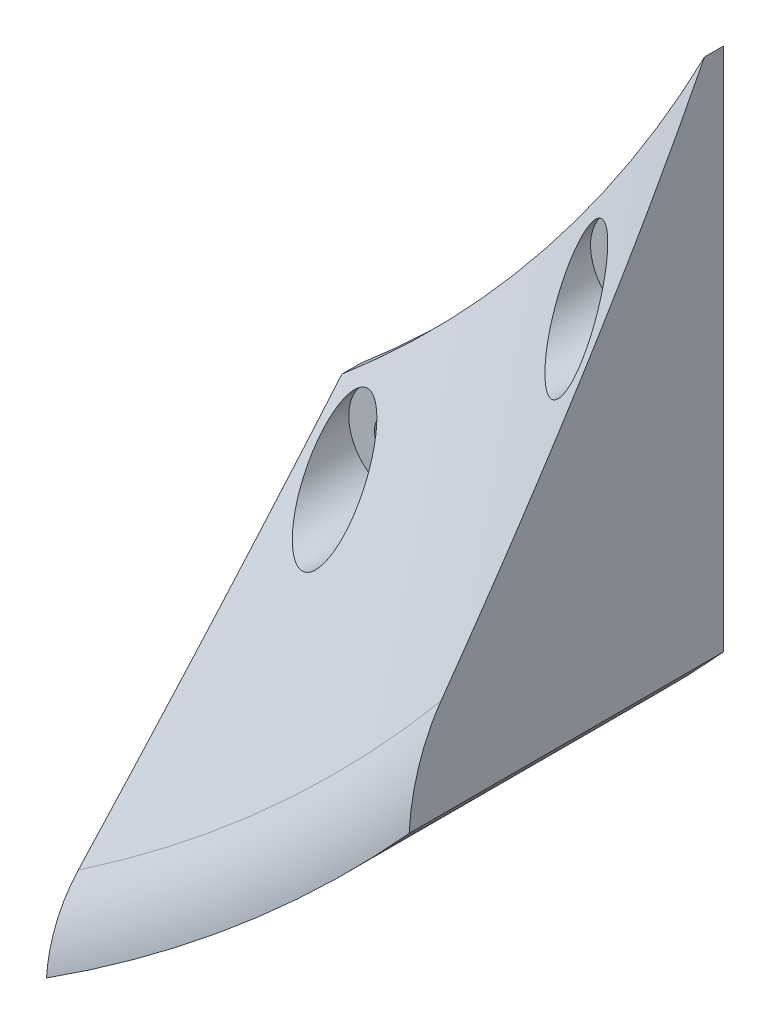
SolidWorks part; units mm, degrees
material "6061 Alloy"
ref_plane "Front Plane" through (0, 0, 0) normal (0, 0, 1) x (1, 0, 0)
ref_plane "Top Plane" through (0, 0, 0) normal (0, 1, 0) x (1, 0, 0)
ref_plane "Right Plane" through (0, 0, 0) normal (1, 0, 0) x (0, 0, -1)
sketch "Sketch1" plane through (0, 0, 0) normal (0, 0, 1) x (1, 0, 0)
  line L1 (-140.9655, 145.0225) -> (-102.8655, 145.0225)
  line L2 (-140.9655, 145.0225) -> (-140.9655, -145.0225)
  line L3 (-140.9655, -145.0225) -> (-102.8655, -145.0225)
  line L4 (-102.8655, 145.0225) -> (-102.8655, -145.0225)
  line L5 (-140.9655, 145.0225) -> (-102.8655, -145.0225) construction
  line L6 (-140.9655, -145.0225) -> (-102.8655, 145.0225) construction
  line L7 (-140.9655, 31.75) -> (140.9655, 31.75)
  line L8 (-140.9655, 31.75) -> (-140.9655, -31.75)
  line L9 (-140.9655, -31.75) -> (140.9655, -31.75)
  line L10 (140.9655, 31.75) -> (140.9655, -31.75)
  line L11 (-140.9655, 31.75) -> (140.9655, -31.75) construction
  line L12 (-140.9655, -31.75) -> (140.9655, 31.75) construction
  line L13 (102.8655, 145.0225) -> (140.9655, 145.0225)
  line L14 (102.8655, 145.0225) -> (102.8655, -145.0225)
  line L15 (102.8655, -145.0225) -> (140.9655, -145.0225)
  line L16 (140.9655, 145.0225) -> (140.9655, -145.0225)
  line L17 (102.8655, 145.0225) -> (140.9655, -145.0225) construction
  line L18 (102.8655, -145.0225) -> (140.9655, 145.0225) construction
  line L19 (-140.9655, -31.75) -> (140.9655, -31.75)
  line L20 (-140.9655, -31.75) -> (-140.9655, -69.85)
  line L21 (-140.9655, -69.85) -> (140.9655, -69.85)
  line L22 (140.9655, -31.75) -> (140.9655, -69.85)
  circle A0 centre (0, 0) radius 177.8
  circle A7 centre (0, -38.1) radius 25.4 construction
  circle A8 centre (-25.4, -38.1) radius 2.3813
  circle A9 centre (25.4, -38.1) radius 2.3813
  circle A10 centre (0, -38.1) radius 2.3812
  point P3 (-121.9155, 0)
  point P12 (121.9155, 0)
  dimension "D1" = 355.6
  dimension "D5" = 50.8
  dimension "D6" = 38.1
  dimension "D7" = 281.9311
  dimension "D10" = 4.7625
  dimension "D8" = 4.7625
  dimension "D9" = 4.7625
  dimension "D2" = 38.1
  dimension "D3" = 38.1
  dimension "D4" = 63.5
  dimension "D12" = 38.1
extrude "Boss-Extrude1" add sketch "Sketch1" along normal blind 3.175 contours L4 A0 L2 L7 | L2 L9 L4 L7 | L14 L7 L4 L9 A8 | L2 A0 L4 L9 | L16 A0 L14 L7 | L7 L14 L9 L10 | L14 A0 L16 L9 | L19 A10 L9 L4 L21 L14 A9 A8 | L2 L21 L4 L9 | L14 L21 L16 L9 region at (-120.723, 80.7079, 0) region at (0, 0, 0) region at (-121.9155, 0, 0) region at (120.723, 80.7079, 0) region at (-119.9486, -100.1295, 0) region at (0, -50.8872, 0) region at (-121.9155, -50.8, 0) region at (121.9155, 0, 0) region at (121.9155, -50.8, 0) region at (119.9486, -100.1295, 0)
sketch "Sketch2" plane through (0, 0, 3.175) normal (0, 0, 1) x (1, 0, 0)
  line L0 (-140.9655, -103.066) -> (-140.9655, -108.3585)
  line L1 (-140.9655, 108.3585) -> (-140.9655, -108.3585) construction
  line L2 (-102.8655, -141.1119) -> (-102.8655, -145.0225)
  line L3 (102.8655, -141.1119) -> (102.8655, -145.0225)
  line L4 (102.8655, -69.85) -> (102.8655, -145.0225) construction
  line L5 (140.9655, -103.066) -> (140.9655, -108.3585)
  line L6 (140.9655, 108.3585) -> (140.9655, -108.3585) construction
  line L7 (-102.8655, -69.85) -> (-102.8655, -145.0225) construction
  circle A0 centre (0, 0) radius 177.8
  circle A1 centre (0, 0) radius 174.625
  line M3 (-140.9655, 108.3585) -> (-140.9655, -108.3585)
  arc M4 (-140.9655, -108.3585) -> (-102.8655, -145.0225) centre (0, 0) ccw
  line M5 (-102.8655, -145.0225) -> (-102.8655, -69.85)
  line M7 (102.8655, -69.85) -> (102.8655, -145.0225)
  arc M8 (102.8655, -145.0225) -> (140.9655, -108.3585) centre (0, 0) ccw
  line M9 (140.9655, -108.3585) -> (140.9655, 108.3585)
  dimension "D1" = 355.6
  dimension "D2" = 349.25
extrude "Boss-Extrude2" add sketch "Sketch2" along normal blind 50.8 contours A1 M3 M4 M5 | A1 M7 M8 M9 region at (-122.8631, -125.3578, 3.175) region at (122.8631, -125.3578, 3.175)
sketch "Sketch3" plane through (0, 0, 3.175) normal (0, 0, 1) x (1, 0, 0)
  circle A0 centre (0, 0) radius 174.625
  circle A1 centre (0, 0) radius 203.8293
  dimension "D1" = 349.25
extrude "Cut-Extrude1" cut sketch "Sketch3" along normal through all and the other way through all
sketch "Sketch5" plane through (0, 0, 3.175) normal (0, 0, 1) x (1, 0, 0)
  line L0 (0, 165.1) -> (0, -165.1) construction
  line L1 (102.8655, -69.85) -> (102.8655, -141.1119) construction
  circle A0 centre (0, 0) radius 165.1 construction
  circle A1 centre (134.6155, -95.5859) radius 2.3813
  circle A2 centre (109.2155, -123.8143) radius 2.3813
  circle A3 centre (-134.6155, -95.5859) radius 2.3813
  circle A4 centre (-109.2155, -123.8143) radius 2.3813
  arc A5 (140.9655, 103.066) -> (102.8655, 141.1119) centre (0, 0) ccw construction
  dimension "D1" = 330.2
  dimension "D3" = 4.7625
  dimension "D4" = 4.7625
  dimension "D2" = 25.4
  dimension "D5" = 6.35
extrude "Cut-Extrude3" cut sketch "Sketch5" against normal through all
sketch "Sketch6" plane through (0, 0, 3.175) normal (0, 0, 1) x (1, 0, 0)
  line L0 (-102.8655, 141.1119) -> (-102.8655, 31.75) construction
  line L1 (-102.8655, 90.3119) -> (102.8655, 90.3119)
  line L2 (-102.8655, 90.3119) -> (-102.8655, 64.9119)
  line L3 (-102.8655, 64.9119) -> (102.8655, 64.9119)
  line L4 (102.8655, 90.3119) -> (102.8655, 64.9119)
  line L5 (102.8655, 141.1119) -> (102.8655, 31.75) construction
  dimension "D1" = 25.4
  dimension "D2" = 50.8
extrude "Boss-Extrude3" add sketch "Sketch6" against normal blind 3.175
sketch "Sketch7" plane through (0, 0, 3.175) normal (0, 0, 1) x (1, 0, 0)
  line L0 (102.8655, 90.3119) -> (-102.8655, 90.3119) construction
  line L1 (-157.8266, 90.3119) -> (153.0605, 90.3119)
  line L2 (-157.8266, 90.3119) -> (-157.8266, 162.3702)
  line L3 (-157.8266, 162.3702) -> (153.0605, 162.3702)
  line L4 (153.0605, 90.3119) -> (153.0605, 162.3702)
extrude "Cut-Extrude4" [suppressed] cut sketch "Sketch7" against normal through all
sketch "Sketch8" plane through (0, 0, 3.175) normal (0, 0, 1) x (1, 0, 0)
  circle A0 centre (0, -38.1) radius 38.1 construction
  circle A1 centre (-38.1, -38.1) radius 2.3812
  circle A2 centre (0, -38.1) radius 50.8 construction
  circle A3 centre (-50.8, -38.1) radius 2.3812
  circle A4 centre (0, -38.1) radius 12.7 construction
  circle A5 centre (12.7, -38.1) radius 2.3812
  circle A6 centre (-12.7, -38.1) radius 2.3812
  dimension "D1" = 76.2
  dimension "D2" = 4.7625
  dimension "D3" = 101.6
  dimension "D4" = 4.7625
  dimension "D5" = 25.4
  dimension "D6" = 4.7625
  dimension "D7" = 4.7625
extrude "Cut-Extrude5" cut sketch "Sketch8" against normal through all
sketch "Sketch9" plane through (0, 0, 3.175) normal (0, 0, 1) x (1, 0, 0)
  line L0 (102.8655, -69.85) -> (102.8655, -141.1119) construction
  line L1 (-102.8655, -69.85) -> (102.8655, -69.85)
  line L2 (-102.8655, -69.85) -> (-102.8655, -107.95)
  line L3 (-102.8655, -107.95) -> (102.8655, -107.95)
  line L4 (102.8655, -69.85) -> (102.8655, -107.95)
  dimension "D1" = 38.1
extrude "Boss-Extrude4" add sketch "Sketch9" against normal blind 3.175
sketch "Sketch10" plane through (0, 0, 3.175) normal (0, 0, 1) x (1, 0, 0)
  circle A0 centre (0, -76.2) radius 6.35
  circle A1 centre (0, -38.1) radius 2.3812 construction
  circle A2 centre (0, -76.2) radius 25.4 construction
  circle A3 centre (0, -76.2) radius 38.1 construction
  circle A4 centre (-25.4, -76.2) radius 2.3813
  circle A5 centre (-38.1, -76.2) radius 2.3812
  circle A6 centre (25.4, -76.2) radius 2.3813
  dimension "D1" = 38.1
  dimension "D2" = 12.7
  dimension "D3" = 50.8
  dimension "D4" = 76.2
  dimension "D5" = 4.7625
  dimension "D6" = 4.7625
  dimension "D7" = 4.7625
extrude "Cut-Extrude6" cut sketch "Sketch10" against normal through all
sketch "Sketch11" plane through (0, 0, 3.175) normal (0, 0, 1) x (1, 0, 0)
  line L0 (-102.8655, -107.95) -> (102.8655, -107.95) construction
  line L1 (-26.6655, -107.95) -> (26.6655, -107.95)
  line L2 (-26.6655, -107.95) -> (-26.6655, -139.7)
  line L3 (-26.6655, -139.7) -> (26.6655, -139.7)
  line L4 (26.6655, -107.95) -> (26.6655, -139.7)
  line L5 (-102.8655, -107.95) -> (-102.8655, -141.1119) construction
  line L6 (102.8655, -107.95) -> (102.8655, -141.1119) construction
  dimension "D1" = 31.75
  dimension "D2" = 76.2
  dimension "D3" = 76.2
extrude "Boss-Extrude5" add sketch "Sketch11" against normal blind 3.175
fillet "Fillet1" radius 10.16 4 edges at (26.6655, -107.95, 1.5875) (-26.6655, -107.95, 1.5875) (-26.6655, -139.7, 1.5875) (26.6655, -139.7, 1.5875)
sketch "Sketch12" plane through (0, 0, 3.175) normal (0, 0, 1) x (1, 0, 0)
  line L1 (-12.7, -63.5) -> (12.7, -63.5) construction
  line L2 (-12.7, -63.5) -> (-12.7, -88.9) construction
  line L3 (-12.7, -88.9) -> (12.7, -88.9) construction
  line L4 (12.7, -63.5) -> (12.7, -88.9) construction
  circle A0 centre (-25.4, -76.2) radius 6.35
  circle A1 centre (25.4, -76.2) radius 6.35
  circle A2 centre (0, -76.2) radius 6.35 construction
  circle A3 centre (-8.6678, -67.5323) radius 2.3812
  circle A7 centre (8.6677, -67.5322) radius 2.3813
  circle A8 centre (8.6678, -84.8677) radius 2.3812
  circle A9 centre (-8.6677, -84.8677) radius 2.3812
  point P23 (0, -76.2)
  point P24 (0, -76.2)
  dimension "D1" = 12.7
  dimension "D2" = 12.7
  dimension "D7" = 4.0323
  dimension "D9" = 4.7625
  dimension "D3" = 12.7
  dimension "D4" = 25.4
  dimension "D5" = 12.7
  dimension "D6" = 25.4
  dimension "D8" = 4.0323
  dimension "D10" = 4
extrude "Cut-Extrude7" cut sketch "Sketch12" against normal through all
fillet "Fillet2" radius 2.54 2 edges at (102.8655, 141.1119, 1.5875) (-102.8655, 141.1119, 1.5875)
sketch "Sketch13" plane through (0, 0, 3.175) normal (0, 0, 1) x (1, 0, 0)
  line L0 (-140.9655, -16.1069) -> (140.9655, -16.1069) construction
  line L1 (-140.9655, 103.066) -> (-140.9655, -103.066) construction
  line L2 (140.9655, 103.066) -> (140.9655, -103.066) construction
  text T0 "7042" font "Aero" height 25.4
extrude "Cut-Extrude8" cut sketch "Sketch13" against normal through all
sketch "Sketch14" plane through (0, 0, 3.175) normal (0, 0, 1) x (1, 0, 0)
  line L1 (-12.3972, 11.8715) -> (-9.6379, 11.8715)
  line L2 (-12.3972, 11.8715) -> (-12.3972, 3.9079)
  line L3 (-12.3972, 3.9079) -> (-9.6379, 3.9079)
  line L4 (-9.6379, 11.8715) -> (-9.6379, 3.9079)
  line L5 (-16.0587, -11.8105) -> (-13.5317, -11.8105)
  line L6 (-16.0587, -11.8105) -> (-16.0587, -17.7494)
  line L7 (-16.0587, -17.7494) -> (-13.5317, -17.7494)
  line L8 (-13.5317, -11.8105) -> (-13.5317, -17.7494)
extrude "Boss-Extrude6" add sketch "Sketch14" against normal blind 3.175
fillet "Fillet3" radius 2.54 6 edges at (-102.8655, 90.3119, 1.5875) (102.8655, 90.3119, 1.5875) (102.8655, 31.75, 1.5875) (102.8655, 64.9119, 1.5875) (-102.8655, 31.75, 1.5875) (-102.8655, 64.9119, 1.5875)
sketch "Sketch15" plane through (0, 0, 3.175) normal (0, 0, 1) x (1, 0, 0)
  line L0 (-140.9655, -30.7998) -> (-140.9655, -128.1365)
  line L1 (-140.9655, 103.066) -> (-140.9655, -103.066) construction
  line L2 (140.9655, -44.4978) -> (140.9655, -128.1365)
  line L3 (140.9655, 103.066) -> (140.9655, -103.066) construction
  line L4 (-102.8655, -107.95) -> (-102.8655, -160.34)
  line L5 (102.8655, -107.95) -> (102.8655, -160.34)
  circle A0 centre (0, 0) radius 158.75
  circle A1 centre (0, 0) radius 190.5
  circle A2 centre (-134.6155, -95.5859) radius 2.3813
  circle A3 centre (-109.2155, -123.8143) radius 2.3812
  circle A4 centre (109.2155, -123.8143) radius 2.3813
  circle A5 centre (109.2155, -123.8143) radius 2.3813 construction
  circle A6 centre (134.6155, -95.5859) radius 2.3813
  dimension "D1" = 317.5
  dimension "D2" = 381
extrude "Boss-Extrude7" add sketch "Sketch15" along normal blind 33.02 contours L0 A1 L4 A0 | L5 A1 L2 A0 region at (-122.9806, -122.07, 3.175) region at (122.9806, -122.07, 3.175)
sketch "Sketch16" plane through (0, 0, 3.175) normal (0, 0, 1) x (1, 0, 0)
  line L1 (-160.8587, 42.3801) -> (207.6811, 42.3801)
  line L2 (-160.8587, 42.3801) -> (-160.8587, 189.4949)
  line L3 (-160.8587, 189.4949) -> (207.6811, 189.4949)
  line L4 (207.6811, 42.3801) -> (207.6811, 189.4949)
  circle A0 centre (0, 0) radius 227.7547
extrude "Cut-Extrude9" cut sketch "Sketch16" against normal through all contours L1 A0 | L1 A0 | A0 L1 L4 L3 L2 region at (15.0013, 112.5626, 3.175) region at (-7.1756, -66.5524, 3.175)
sketch "Sketch17" plane through (0, 0, 36.195) normal (0, 0, 1) x (1, 0, 0)
  circle A0 centre (124.015, -121.333) radius 87.1955
extrude "Cut-Extrude10" cut sketch "Sketch17" against normal through all
chamfer "Chamfer1" distance 27.94 angle 48 1 edges at (-124.2463, -98.8151, 36.195) first distance on face at (-106.8343, -123.8143, 36.195)
sketch "Sketch18" plane through (0, 0, 3.175) normal (0, 0, -1) x (-1, 0, 0)
  circle A0 centre (0, 0) radius 171.45 construction
  circle A2 centre (134.6155, -95.5859) radius 5.08
  circle A6 centre (109.2155, -123.8143) radius 5.08
  circle A7 centre (109.2155, -123.8143) radius 2.3813 construction
  dimension "D1" = 342.9
  dimension "D2" = 10.16
  dimension "D3" = 10.16
extrude "Cut-Extrude12" cut sketch "Sketch18" against normal blind 33.02 from offset 2.54 offset against normal yes
fillet "Fillet4" radius 10.16 1 edges at (-123.0536, -140.3958, 36.195)
mirror "Mirror1" about plane through (-102.8655, 0, 3.175) normal (1, 0, 0) of bodies 124
sketch "Sketch19" plane through (-64.7655, 0, 0) normal (1, 0, 0) x (0, 0, -1)
  circle A0 centre (-10.6035, -117.9401) radius 70.9948
extrude "Cut-Extrude13" cut sketch "Sketch19" against normal through all from vertex starting at point (-102.8655, -152.1831, 32.8602)
